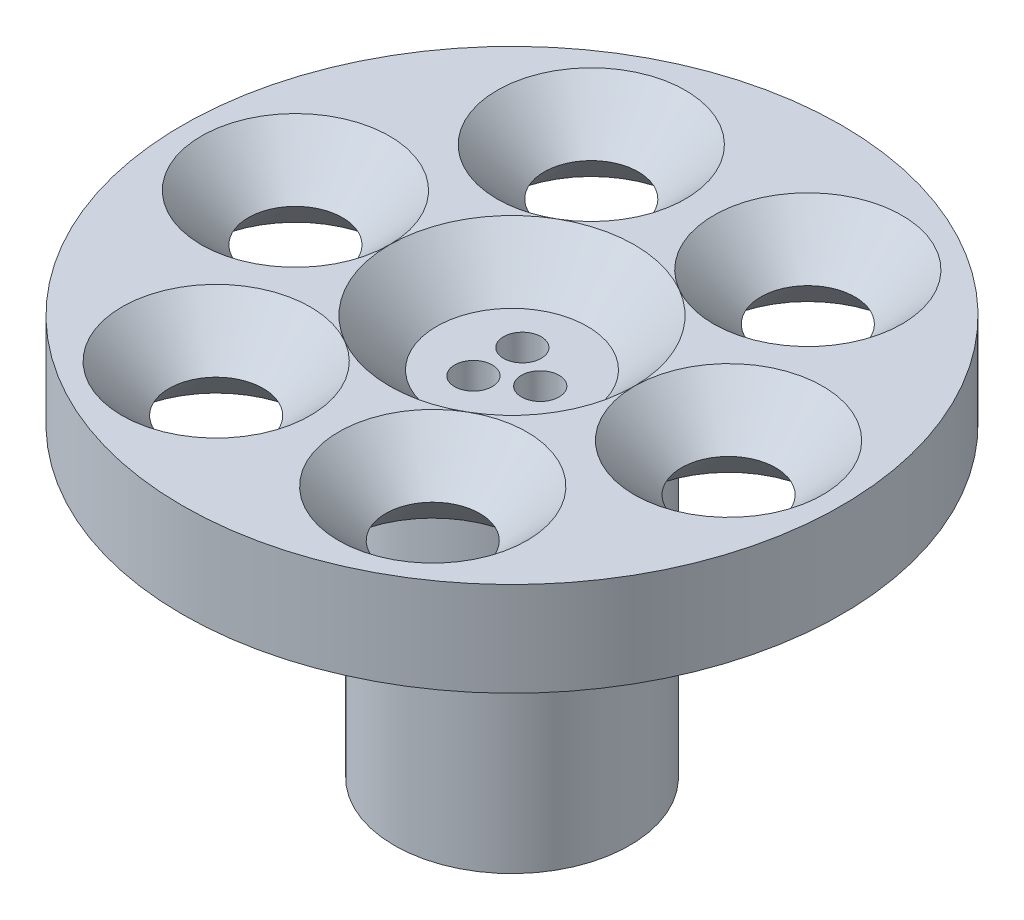
SolidWorks part; units mm, degrees
ref_plane "Front Plane" through (0, 0, 0) normal (0, 0, 1) x (1, 0, 0)
ref_plane "Top Plane" through (0, 0, 0) normal (0, 1, 0) x (1, 0, 0)
ref_plane "Right Plane" through (0, 0, 0) normal (1, 0, 0) x (0, 0, -1)
sketch "Sketch1" plane through (0, 0, 0) normal (0, 1, 0) x (1, 0, 0)
  circle A0 centre (0, 0) radius 12.5
  circle A1 centre (0, 0) radius 5.5
  circle A2 centre (0, 0) radius 3
  circle A3 centre (3, 0) radius 2
  circle A4 centre (-1.5, -2.5981) radius 2
  circle A5 centre (-1.5, 2.5981) radius 2
  point P13 (0, 0)
  dimension "D1" = 3
extrude "Boss-Extrude1" add sketch "Sketch1" along normal blind 42.5 contours A1 A5 A2 A3 A4 | A5 A2 A4 A3 | A0 A1 region at (-12.1464, 0, 0) region at (-5.3444, 0, 0) region at (0, 0, 0)
sketch "Sketch2" plane through (0, 0, 0) normal (0, -1, 0) x (1, 0, 0)
  circle A0 centre (0, 0) radius 5.5
extrude "Cut-Extrude1" cut sketch "Sketch2" against normal blind 1.5
sketch "Sketch3" plane through (0, 42.5, 0) normal (0, 1, 0) x (1, 0, 0)
  circle A0 centre (0, 0) radius 35
  circle A1 centre (0, 0) radius 12.5
  circle A2 centre (3, 0) radius 2
  circle A3 centre (-1.5, -2.5981) radius 2
  circle A4 centre (-1.5, 2.5981) radius 2
  circle M5 centre (0, 0) radius 12.5
extrude "Boss-Extrude3" add sketch "Sketch3" against normal blind 10 contours A0 M5 region at (-34.0101, 42.5, 0)
sketch "Sketch4" plane through (0, 42.5, 0) normal (0, 1, 0) x (1, 0, 0)
  circle A0 centre (0, 0) radius 35
  circle A1 centre (0, 0) radius 23
  circle A2 centre (-23, 0) radius 5
  circle A3 centre (-11.5, 19.9186) radius 5
  circle A4 centre (11.5, 19.9186) radius 5
  circle A5 centre (23, 0) radius 5
  circle A6 centre (11.5, -19.9186) radius 5
  circle A7 centre (-11.5, -19.9186) radius 5
  point P18 (0, 0)
  dimension "D1" = 6
extrude "Cut-Extrude5" cut sketch "Sketch4" against normal blind 10 contours A3 | A4 | A5 | A6 | A7 | A2
chamfer "Chamfer7" distance 5 angle 45 12 edges at (-23, 42.5, 5) (11.5, 32.5, 24.9186) (23, 32.5, 5) (11.5, 32.5, -14.9186) (-11.5, 32.5, -14.9186) (-23, 32.5, 5) (-11.5, 32.5, 24.9186) (-11.5, 42.5, 24.9186) (11.5, 42.5, 24.9186) (23, 42.5, 5) (11.5, 42.5, -14.9186) (-11.5, 42.5, -14.9186)
sketch "Sketch7" plane through (0, 42.5, 0) normal (0, 1, 0) x (1, 0, 0)
  circle A0 centre (0, 0) radius 5.5
  circle A1 centre (0, 0) radius 8
  circle A2 centre (3, 0) radius 2
  circle A3 centre (-1.5, -2.5981) radius 2
  circle A4 centre (-1.5, 2.5981) radius 2
  circle M9 centre (-1.5, 2.5981) radius 2
  circle M10 centre (3, 0) radius 2
  circle M11 centre (-1.5, -2.5981) radius 2
extrude "Cut-Extrude6" cut sketch "Sketch7" against normal blind 5 contours A1 A0 | A0 M9 M11 M10 region at (0, 42.5, 0) region at (-7.7737, 42.5, 0)
chamfer "Chamfer8" distance 5 angle 45 1 edges at (0, 42.5, 8)
